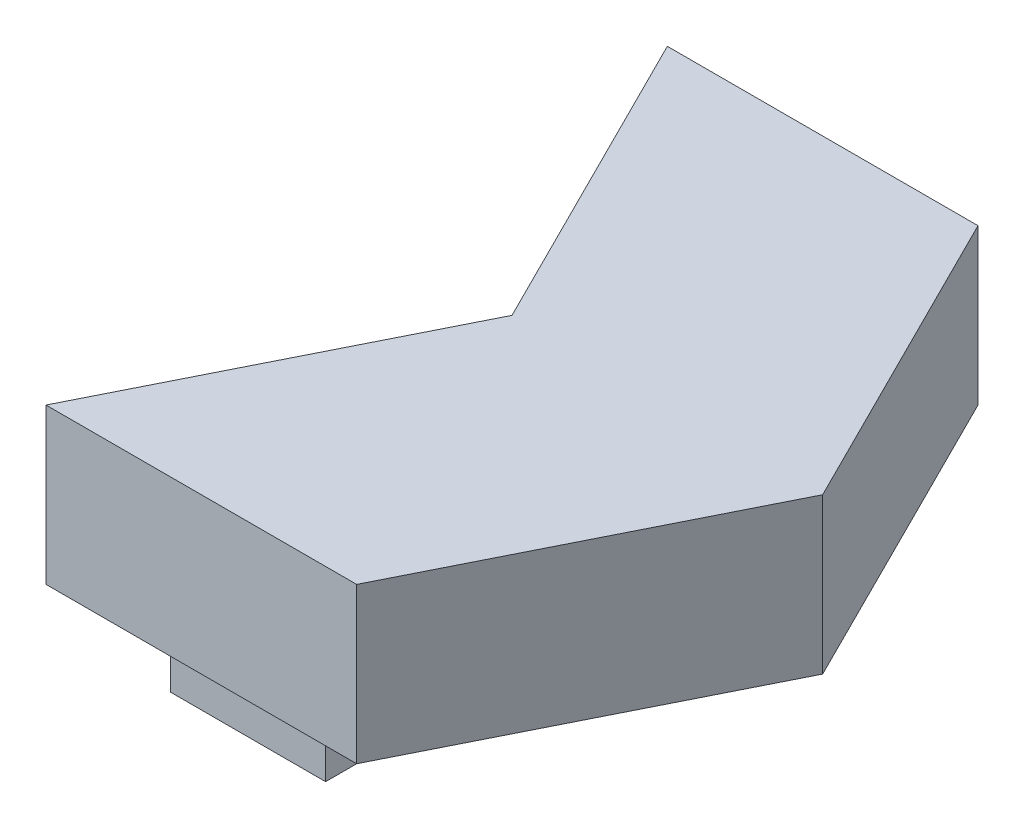
SolidWorks part; units mm, degrees
ref_plane "Front Plane" through (0, 0, 0) normal (0, 0, 1) x (1, 0, 0)
ref_plane "Top Plane" through (0, 0, 0) normal (0, 1, 0) x (1, 0, 0)
ref_plane "Right Plane" through (0, 0, 0) normal (1, 0, 0) x (0, 0, -1)
sketch "Sketch1" plane through (0, 0, 0) normal (0, 1, 0) x (1, 0, 0)
  line L0 (0, 0) -> (12.7, 0)
  line L1 (12.7, 0) -> (19.05, 12.7)
  line L2 (19.05, 12.7) -> (12.7, 25.4)
  line L3 (12.7, 25.4) -> (0, 25.4)
  line L4 (0, 25.4) -> (6.35, 12.7)
  line L5 (6.35, 12.7) -> (0, 0)
  dimension "D1" = 12.7
  dimension "D2" = 25.4
  dimension "D3" = 6.35
  dimension "D5" = 12.7
extrude "Boss-Extrude1" add sketch "Sketch1" along normal blind 6.35
sketch "Sketch2" plane through (0, 0, 0) normal (0, -1, 0) x (1, 0, 0)
  line L0 (19.05, -12.7) -> (6.35, -12.7) construction
  line L1 (6.35, -12.7) -> (0, 0) construction
  circle A0 centre (12.192, -12.7) radius 5.127
  dimension "D1" = 10.254
  dimension "D2" = 5.842
extrude "Cut-Extrude1" cut sketch "Sketch2" against normal blind 2.7 contours A0
sketch "Sketch3" plane through (0, 0, 0) normal (0, -1, 0) x (1, 0, 0)
  line L8 (11.1065, -17.7108) -> (8.8347, -16.5749)
  line L9 (11.1065, -17.7108) -> (9.4026, -21.1185)
  line L10 (8.8347, -16.5749) -> (7.1308, -19.9826)
  line L11 (9.4026, -21.1185) -> (7.1308, -19.9826)
  line L12 (19.05, -12.7) -> (12.7, -25.4) construction
  circle A3 centre (12.192, -12.7) radius 5.127 construction
  dimension "D1" = 2.54
  dimension "D2" = 3.81
extrude "Cut-Extrude2" cut sketch "Sketch3" against normal blind 2.7
ref_plane "MidPlane" through (0, 0, -12.7) normal (0, 0, -1) x (-1, 0, 0)
sketch "Sketch4" plane through (0, 0, 0) normal (0, -1, 0) x (1, 0, 0)
  line L0 (12.7, -25.4) -> (0, -25.4) construction
  line L1 (10.16, -24.13) -> (3.81, -24.13)
  line L2 (10.16, -24.13) -> (10.16, -21.59)
  line L3 (10.16, -21.59) -> (3.81, -21.59)
  line L4 (3.81, -24.13) -> (3.81, -21.59)
  line L5 (0, -4.8895) -> (0, 4.8895) construction
  dimension "D1" = 2.54
  dimension "D2" = 6.35
  dimension "D3" = 1.27
  dimension "D4" = 3.81
extrude "Boss-Extrude2" add sketch "Sketch4" along normal blind 2.54
mirror "Mirror1" about plane through (0, 0, -12.7) normal (0, 0, -1) of "Boss-Extrude2"
equation "\"Arrow Height\"= 1in"
equation "\"Button Height\"= 2in"
equation "\"Button Width\"= 4in"
equation "\"Haptic Diameter\"= 10mm"
equation "\"Haptic Thickness\"= 2.7mm"
equation "\"D2@Sketch1\"=\"Arrow Height\""
equation "\"D5@Sketch1\"=\"Arrow Height\"/2"
equation "\"D1@Sketch2\"=\"Haptic Diameter\" + .01in"
equation "\"D1@Cut-Extrude1\"=\"Haptic Thickness\""
equation "\"D1@Cut-Extrude2\"=\"Haptic Thickness\""
